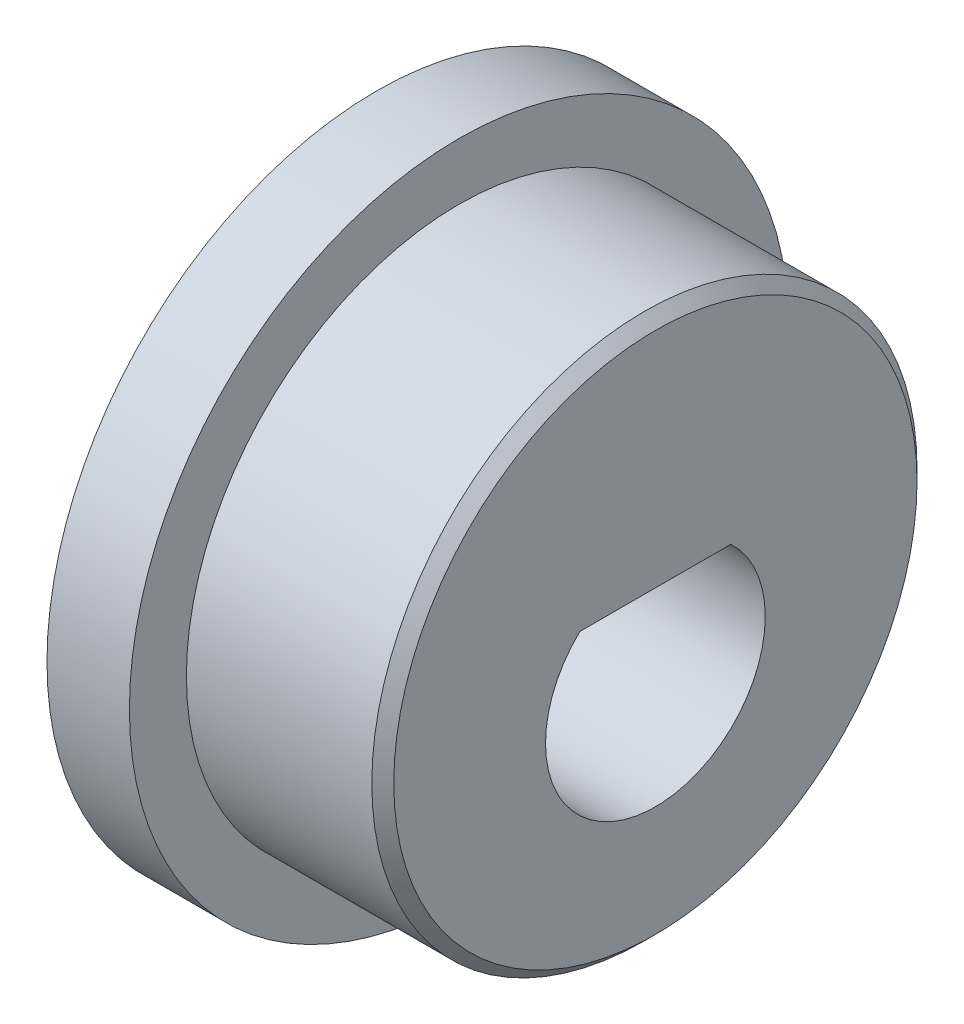
SolidWorks part; units mm, degrees
ref_plane "Ebene vorne" through (0, 0, 0) normal (0, 0, 1) x (1, 0, 0)
ref_plane "Ebene oben" through (0, 0, 0) normal (0, 1, 0) x (1, 0, 0)
ref_plane "Ebene rechts" through (0, 0, 0) normal (1, 0, 0) x (0, 0, -1)
sketch "Skizze1" plane through (0, 0, 0) normal (1, 0, 0) x (0, 0, -1)
  circle A0 centre (0, 1.5) radius 9.925
  dimension "D2" = 19.85
  dimension "D1" = 1.5
extrude "Aufsatz-Linear austragen1" add sketch "Skizze1" along normal blind 7.15
sketch "Skizze2" plane through (0, 0, 0) normal (-1, 0, 0) x (0, 0, 1)
  circle A0 centre (0, 1.5) radius 12
  dimension "D1" = 24
extrude "Aufsatz-Linear austragen2" add sketch "Skizze2" along normal blind 3
sketch "Skizze3" plane through (7.15, 0, 0) normal (1, 0, 0) x (0, 0, -1)
  line L0 (-2.75, 2.9047) -> (2.75, 2.9047)
  arc A0 (-2.75, 2.9047) -> (2.75, 2.9047) centre (0, 0) ccw
  dimension "D1" = 4
  dimension "D2" = 5.5
extrude "Schnitt-Linear austragen2" cut sketch "Skizze3" against normal through all both and the other way through all
chamfer "Fase1" distance 0.4 angle 45 1 edges at (7.15, 1.5, -9.925)
